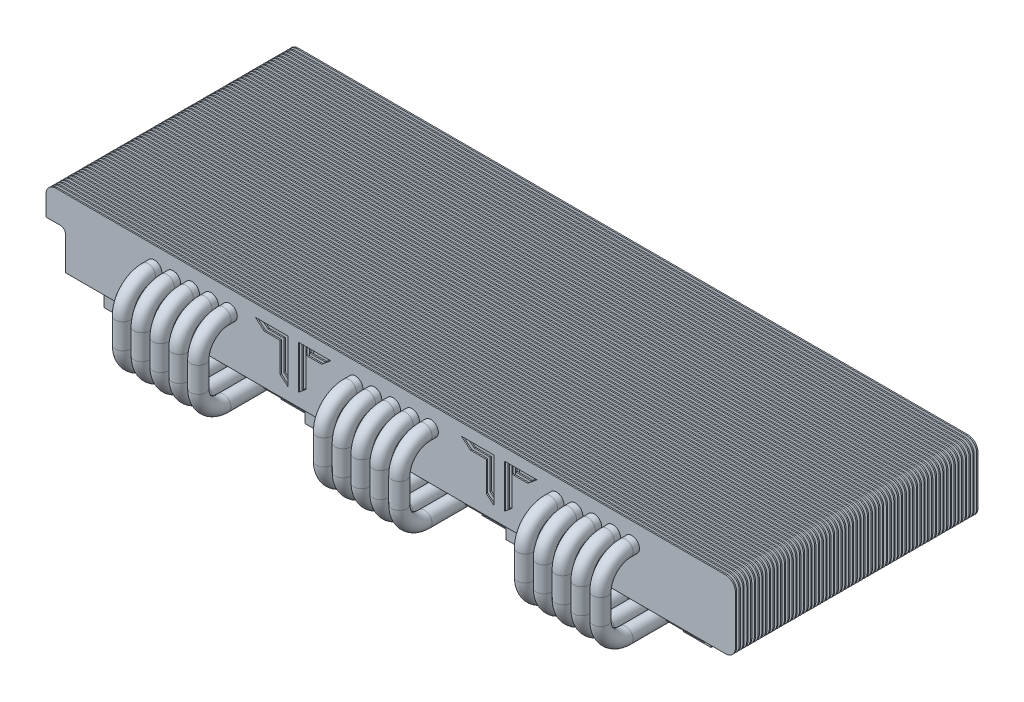
SolidWorks part; units mm, degrees
ref_plane "Front Plane" through (0, 0, 0) normal (0, 0, 1) x (1, 0, 0)
ref_plane "Top Plane" through (0, 0, 0) normal (0, 1, 0) x (1, 0, 0)
ref_plane "Right Plane" through (0, 0, 0) normal (1, 0, 0) x (0, 0, -1)
sketch "Sketch1" plane through (0, 0, 0) normal (0, 1, 0) x (1, 0, 0)
  line L0 (0, -32.7) -> (0, 32.7)
  line L1 (0, 32.7) -> (-11, 32.7)
  line L2 (-11, 32.7) -> (-11, -32.7)
  line L3 (-11, -32.7) -> (0, -32.7)
  line L4 (-12.4, 32.7) -> (-78.9, 32.7)
  line L5 (-14.15, 10.05) -> (-52.15, 10.05)
  line L6 (-14.15, 10.05) -> (-14.15, -27.95)
  line L7 (-14.15, -27.95) -> (-52.15, -27.95)
  line L8 (-52.15, 10.05) -> (-52.15, -27.95)
  line L9 (-78.9, 32.7) -> (-78.9, -35.3)
  line L10 (-78.9, -35.3) -> (-61.9, -35.3)
  line L11 (-61.9, -35.3) -> (-61.9, 16.55)
  line L12 (-61.9, 16.55) -> (-12.4, 16.55)
  line L13 (-12.4, 16.55) -> (-12.4, 32.7)
  line L14 (80, -32.7) -> (80, 32.7)
  line L15 (80, 32.7) -> (69, 32.7)
  line L16 (69, 32.7) -> (69, -32.7)
  line L17 (69, -32.7) -> (80, -32.7)
  line L18 (67.6, 32.7) -> (1.1, 32.7)
  line L19 (65.85, 10.05) -> (27.85, 10.05)
  line L20 (65.85, 10.05) -> (65.85, -27.95)
  line L21 (65.85, -27.95) -> (27.85, -27.95)
  line L22 (27.85, 10.05) -> (27.85, -27.95)
  line L23 (1.1, 32.7) -> (1.1, -35.3)
  line L24 (1.1, -35.3) -> (18.1, -35.3)
  line L25 (18.1, -35.3) -> (18.1, 16.55)
  line L26 (18.1, 16.55) -> (67.6, 16.55)
  line L27 (67.6, 16.55) -> (67.6, 32.7)
  line L28 (160, -32.7) -> (160, 32.7)
  line L29 (160, 32.7) -> (149, 32.7)
  line L30 (149, 32.7) -> (149, -32.7)
  line L31 (149, -32.7) -> (160, -32.7)
  line L32 (147.6, 32.7) -> (81.1, 32.7)
  line L33 (145.85, 10.05) -> (107.85, 10.05)
  line L34 (145.85, 10.05) -> (145.85, -27.95)
  line L35 (145.85, -27.95) -> (107.85, -27.95)
  line L36 (107.85, 10.05) -> (107.85, -27.95)
  line L37 (81.1, 32.7) -> (81.1, -35.3)
  line L38 (81.1, -35.3) -> (98.1, -35.3)
  line L39 (98.1, -35.3) -> (98.1, 16.55)
  line L40 (98.1, 16.55) -> (147.6, 16.55)
  line L41 (147.6, 16.55) -> (147.6, 32.7)
  dimension "D1" = 65.4
  dimension "D2" = 11
  dimension "D3" = 38
  dimension "D4" = 38
  dimension "D5" = 1.4
  dimension "D6" = 66.5
  dimension "D7" = 68
  dimension "D8" = 17
  dimension "D9" = 16.15
  dimension "D10" = 9.75
  dimension "D11" = 6.5
  dimension "D12" = 3
extrude "Boss-Extrude1" add sketch "Sketch1" against normal blind 4
sketch "Sketch2" plane through (0, 0, 0) normal (0, 1, 0) x (1, 0, 0)
  line L0 (-96.9, 47.65) -> (-96.9, -58.35)
  line L1 (-96.9, 47.65) -> (180.1, 47.65)
  line L2 (-12.4, 32.7) -> (-78.9, 32.7) construction
  line L3 (-78.9, 32.7) -> (-78.9, -35.3) construction
  line L4 (-96.9, -58.35) -> (180.1, -58.35)
  line L5 (180.1, -58.35) -> (180.1, 47.65)
  dimension "D1" = 14.95
  dimension "D2" = 18
  dimension "D3" = 106
  dimension "D4" = 277
extrude "Boss-Extrude2" add sketch "Sketch2" along normal blind 6
sketch "Sketch4" plane through (0, -4, 0) normal (0, -1, 0) x (1, 0, 0)
  line L1 (-52.15, 27.95) -> (-14.15, 27.95)
  line L2 (-52.15, 27.95) -> (-52.15, -10.05)
  line L3 (-52.15, -10.05) -> (-14.15, -10.05)
  line L4 (-14.15, 27.95) -> (-14.15, -10.05)
  line L5 (-11, 32.7) -> (0, 32.7)
  line L6 (-11, 32.7) -> (-11, -32.7)
  line L7 (-11, -32.7) -> (0, -32.7)
  line L8 (0, 32.7) -> (0, -32.7)
  line L9 (27.85, 27.95) -> (65.85, 27.95)
  line L10 (27.85, 27.95) -> (27.85, -10.05)
  line L11 (27.85, -10.05) -> (65.85, -10.05)
  line L12 (65.85, 27.95) -> (65.85, -10.05)
  line L13 (69, 32.7) -> (80, 32.7)
  line L14 (69, 32.7) -> (69, -32.7)
  line L15 (69, -32.7) -> (80, -32.7)
  line L16 (80, 32.7) -> (80, -32.7)
  line L17 (107.85, 27.95) -> (145.85, 27.95)
  line L18 (107.85, 27.95) -> (107.85, -10.05)
  line L19 (107.85, -10.05) -> (145.85, -10.05)
  line L20 (145.85, 27.95) -> (145.85, -10.05)
  line L21 (149, 32.7) -> (160, 32.7)
  line L22 (149, 32.7) -> (149, -32.7)
  line L23 (149, -32.7) -> (160, -32.7)
  line L24 (160, 32.7) -> (160, -32.7)
extrude "Cut-Extrude1" cut sketch "Sketch4" against normal blind 1
sketch "Sketch5" plane through (0, 6, 0) normal (0, 1, 0) x (1, 0, 0)
  line L1 (-96.9, 47.65) -> (180.1, 47.65)
  line L2 (-96.9, 47.65) -> (-96.9, -58.35)
  line L3 (-96.9, -58.35) -> (180.1, -58.35)
  line L4 (180.1, 47.65) -> (180.1, -58.35)
extrude "Cut-Extrude2" cut sketch "Sketch5" against normal blind 6
sketch "Sketch6" plane through (0, 0, 27.95) normal (0, 0, 1) x (1, 0, 0)
  line L0 (-52.15, 0) -> (-14.15, 0) construction
  circle A0 centre (-48.3, 0) radius 3
  dimension "D1" = 6
  dimension "D2" = 3.85
sketch3d "3DSketch1"
  line L0 (-48.3, 0, 27.95) -> (-48.3, 0, 48.35)
  line L1 (-48.3, 10, 58.35) -> (-48.3, 20, 58.35)
  line L2 (-48.3, 30, 48.35) -> (-48.3, 30, -51.65)
  line L3 (-52.15, 0, 27.95) -> (-14.15, 0, 27.95) construction
  arc A0 (-48.3, 0, 48.35) -> (-48.3, 10, 58.35) centre (-48.3, 10, 48.35) ccw
  arc A1 (-48.3, 20, 58.35) -> (-48.3, 30, 48.35) centre (-48.3, 20, 48.35) ccw
  point P7 (-48.3, 0, 58.35)
  point P8 (-58.3, 10, 48.35)
  point P11 (-48.3, 30, 58.35)
  point P12 (-58.3, 20, 48.35)
  dimension "D4" = 10
  dimension "D1" = 110
  dimension "D2" = 30.4
  dimension "D3" = 30
sweep "Sweep1" add profiles "Sketch6" path "3DSketch1"
pattern_linear "LPattern1" count 5 spacing 7.5 along (1, 0, 0) of "Sweep1"
sketch "Sketch7" plane through (0, 0, 27.95) normal (0, 0, 1) x (1, 0, 0)
  line L0 (27.85, 0) -> (65.85, 0) construction
  circle A0 centre (31.7, 0) radius 3
  dimension "D1" = 3.85
sketch3d "3DSketch2"
  line L0 (31.7, 0, 27.95) -> (31.7, 0, 48.35)
  line L1 (31.7, 10, 58.35) -> (31.7, 20, 58.35)
  line L2 (31.7, 30, 48.35) -> (31.7, 30, -51.65)
  arc A0 (31.7, 0, 48.35) -> (31.7, 10, 58.35) centre (31.7, 10, 48.35) ccw
  arc A1 (31.7, 20, 58.35) -> (31.7, 30, 48.35) centre (31.7, 20, 48.35) ccw
  point P7 (31.7, 0, 58.35)
  point P8 (21.7, 10, 48.35)
  point P11 (31.7, 30, 58.35)
  point P12 (21.7, 20, 48.35)
  dimension "D4" = 10
  dimension "D1" = 30
  dimension "D2" = 110
  dimension "D3" = 30.4
sweep "Sweep2" add profiles "Sketch7" path "3DSketch2"
pattern_linear "LPattern7" count 5 spacing 7.5 along (1, 0, 0) of "Sweep2"
sketch "Sketch8" plane through (0, 0, 27.95) normal (0, 0, 1) x (1, 0, 0)
  line L0 (107.85, 0) -> (145.85, 0) construction
  circle A0 centre (111.7, 0) radius 3
  dimension "D1" = 3.85
sketch3d "3DSketch3"
  line L0 (111.7, 0, 27.95) -> (111.7, 0, 48.35)
  line L1 (111.7, 10, 58.35) -> (111.7, 20, 58.35)
  line L2 (111.7, 30, 48.35) -> (111.7, 30, -51.65)
  arc A0 (111.7, 0, 48.35) -> (111.7, 10, 58.35) centre (111.7, 10, 48.35) ccw
  arc A1 (111.7, 20, 58.35) -> (111.7, 30, 48.35) centre (111.7, 20, 48.35) ccw
  point P7 (111.7, 0, 58.35)
  point P8 (101.7, 10, 48.35)
  point P11 (111.7, 30, 58.35)
  point P12 (101.7, 20, 48.35)
  dimension "D4" = 10
  dimension "D1" = 110
  dimension "D2" = 30
  dimension "D3" = 30.4
sweep "Sweep3" add profiles "Sketch8" path "3DSketch3"
pattern_linear "LPattern8" count 5 spacing 7.5 along (1, 0, 0) of "Sweep3"
sketch "Sketch9" plane through (0, 0, 0) normal (0, 1, 0) x (1, 0, 0)
  line L1 (-78.9, -35.3) -> (160, -35.3)
  line L2 (-78.9, -35.3) -> (-78.9, 32.7)
  line L3 (-78.9, 32.7) -> (160, 32.7)
  line L4 (160, -35.3) -> (160, 32.7)
extrude "Boss-Extrude3" add sketch "Sketch9" along normal blind 4
ref_plane "Plane1" through (0, 0, -50.65) normal (0, 0, -1) x (-1, 0, 0)
sketch "Sketch10" plane through (0, 0, -50.65) normal (0, 0, -1) x (-1, 0, 0)
  line L0 (78.9, 4) -> (78.9, -4) construction
  line L1 (-178.8988, 38.0987) -> (87.4, 38.0987)
  line L2 (-182.8988, 34.0987) -> (-182.8988, 14.8784)
  line L3 (-178.8988, 10.8784) -> (87.4, 10.8784)
  line L4 (91.4, 34.0987) -> (91.4, 14.8784)
  arc A0 (87.4, 38.0987) -> (91.4, 34.0987) centre (87.4, 34.0987) cw
  arc A1 (87.4, 10.8784) -> (91.4, 14.8784) centre (87.4, 14.8784) ccw
  arc A2 (-182.8988, 14.8784) -> (-178.8988, 10.8784) centre (-178.8988, 14.8784) ccw
  arc A3 (-178.8988, 38.0987) -> (-182.8988, 34.0987) centre (-178.8988, 34.0987) ccw
  dimension "D1" = 4
  dimension "D2" = 12.5
extrude "Boss-Extrude4" add sketch "Sketch10" against normal blind 0.5
pattern_linear "LPattern9" count 65 spacing 1.5 along (0, 0, 1) of "Boss-Extrude4"
sketch "Sketch11" plane through (0, 0, -50.65) normal (0, 0, -1) x (-1, 0, 0)
  line L0 (91.4, 14.8784) -> (91.4, 34.0987) construction
  line L1 (91.4, 26.1784) -> (85.65, 26.1784)
  line L2 (91.4, 26.1784) -> (91.4, 10.8784)
  line L3 (91.4, 10.8784) -> (83.65, 10.8784)
  line L4 (83.65, 24.1784) -> (83.65, 10.8784)
  line L5 (-178.8988, 10.8784) -> (87.4, 10.8784) construction
  arc A0 (85.65, 26.1784) -> (83.65, 24.1784) centre (85.65, 24.1784) ccw
  point P10 (83.65, 26.1784)
  dimension "D3" = 2
  dimension "D1" = 7.75
  dimension "D2" = 15.3
extrude "Cut-Extrude3" cut sketch "Sketch11" against normal blind 99
sketch "Sketch12" plane through (0, 0, -50.65) normal (0, 0, -1) x (-1, 0, 0)
  line L0 (-103.8833, 33.3055) -> (-100.2877, 30.3055)
  line L1 (-100.2877, 30.3055) -> (-93.9633, 30.3055)
  line L2 (-93.9633, 30.3055) -> (-93.9633, 18.4629)
  line L3 (-93.9633, 18.4629) -> (-90.9633, 15.9599)
  line L4 (-90.9633, 15.9599) -> (-90.9633, 33.3055)
  line L5 (-90.9633, 33.3055) -> (-103.8833, 33.3055)
  line L6 (-88.8791, 35.7618) -> (-88.8791, 13.3787) construction
  line L7 (-83.7948, 18.4629) -> (-86.7948, 15.9599)
  line L8 (-83.7948, 30.3055) -> (-83.7948, 18.4629)
  line L9 (-86.7948, 15.9599) -> (-86.7948, 33.3055)
  line L10 (-73.8749, 33.3055) -> (-77.4705, 30.3055)
  line L11 (-77.4705, 30.3055) -> (-83.7948, 30.3055)
  line L12 (-86.7948, 33.3055) -> (-73.8749, 33.3055)
  line L13 (-21.8833, 33.3055) -> (-18.2877, 30.3055)
  line L14 (-18.2877, 30.3055) -> (-11.9633, 30.3055)
  line L15 (-11.9633, 30.3055) -> (-11.9633, 18.4629)
  line L16 (-11.9633, 18.4629) -> (-8.9633, 15.9599)
  line L17 (-8.9633, 15.9599) -> (-8.9633, 33.3055)
  line L18 (-8.9633, 33.3055) -> (-21.8833, 33.3055)
  line L19 (-1.7948, 18.4629) -> (-4.7948, 15.9599)
  line L20 (-1.7948, 30.3055) -> (-1.7948, 18.4629)
  line L21 (-4.7948, 15.9599) -> (-4.7948, 33.3055)
  line L22 (8.1251, 33.3055) -> (4.5295, 30.3055)
  line L23 (4.5295, 30.3055) -> (-1.7948, 30.3055)
  line L24 (-4.7948, 33.3055) -> (8.1251, 33.3055)
  line L25 (-6.8791, 35.7618) -> (-6.8791, 13.3787) construction
  dimension "D1" = 3
  dimension "D2" = 3
  dimension "D3" = 2
extrude "Cut-Extrude4" cut sketch "Sketch12" against normal blind 99
